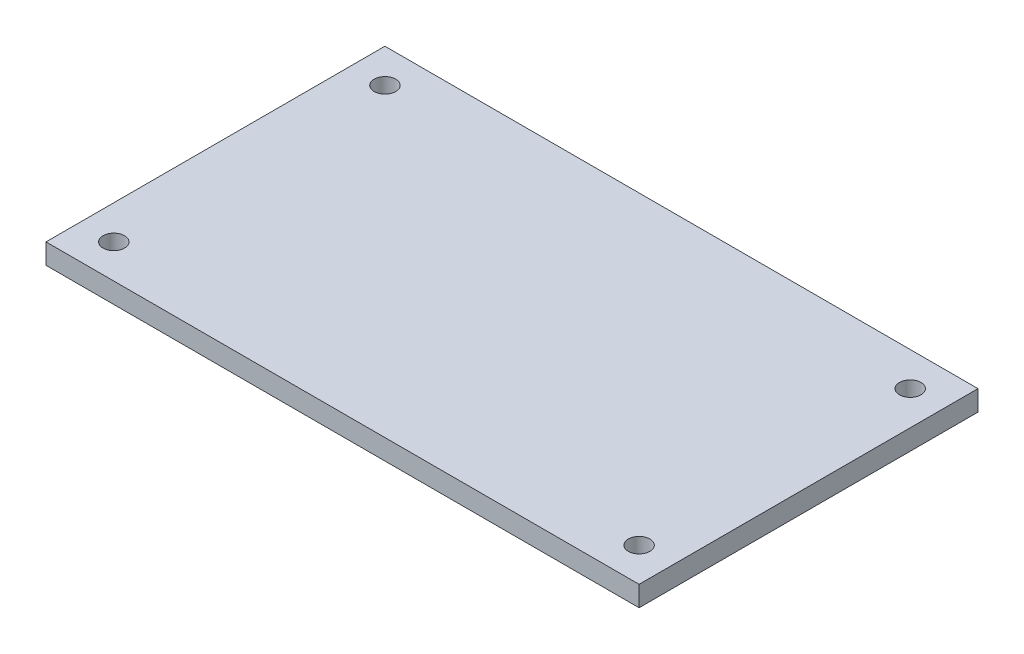
SolidWorks part; units mm, degrees
ref_plane "Front Plane" through (0, 0, 0) normal (0, 0, 1) x (1, 0, 0)
ref_plane "Top Plane" through (0, 0, 0) normal (0, 1, 0) x (1, 0, 0)
ref_plane "Right Plane" through (0, 0, 0) normal (1, 0, 0) x (0, 0, -1)
sketch "Sketch1" plane through (0, 0, 0) normal (0, 1, 0) x (1, 0, 0)
  line L0 (-55, 0) -> (55, 0) construction
  line L1 (-87.5, 50) -> (87.5, 50)
  line L2 (-87.5, 50) -> (-87.5, -50)
  line L3 (-87.5, -50) -> (87.5, -50)
  line L4 (87.5, 50) -> (87.5, -50)
  line L5 (-87.5, 50) -> (87.5, -50) construction
  line L6 (-87.5, -50) -> (87.5, 50) construction
  line L7 (0, -55) -> (0, 55) construction
  circle A0 centre (-77.5, -40) radius 3.175
  circle A1 centre (-77.5, 40) radius 3.175
  circle A2 centre (77.5, 40) radius 3.175
  circle A3 centre (77.5, -40) radius 3.175
  circle A4 centre (-63.5, 25.4) radius 3.175 construction
  circle A5 centre (-63.5, -25.4) radius 3.175 construction
  circle A6 centre (63.5, -25.4) radius 3.175 construction
  circle A7 centre (63.5, 25.4) radius 3.175 construction
  point P0 (0, 0)
  dimension "D3" = 6.35
  dimension "D1" = 100
  dimension "D2" = 175
  dimension "D4" = 40
  dimension "D5" = 77.5
  dimension "D6" = 25.4
  dimension "D7" = 63.5
extrude "Boss-Extrude1" add sketch "Sketch1" along normal blind 6
sketch "Sketch2" plane through (0, 6, 0) normal (0, 1, 0) x (1, 0, 0)
  line L0 (-55, 0) -> (55, 0) construction
  line L1 (0, -55) -> (0, 55) construction
  circle A0 centre (-77.5, 40) radius 5
  circle A1 centre (-77.5, -40) radius 5
  circle A2 centre (77.5, -40) radius 5
  circle A3 centre (77.5, 40) radius 5
  dimension "D1" = 10
